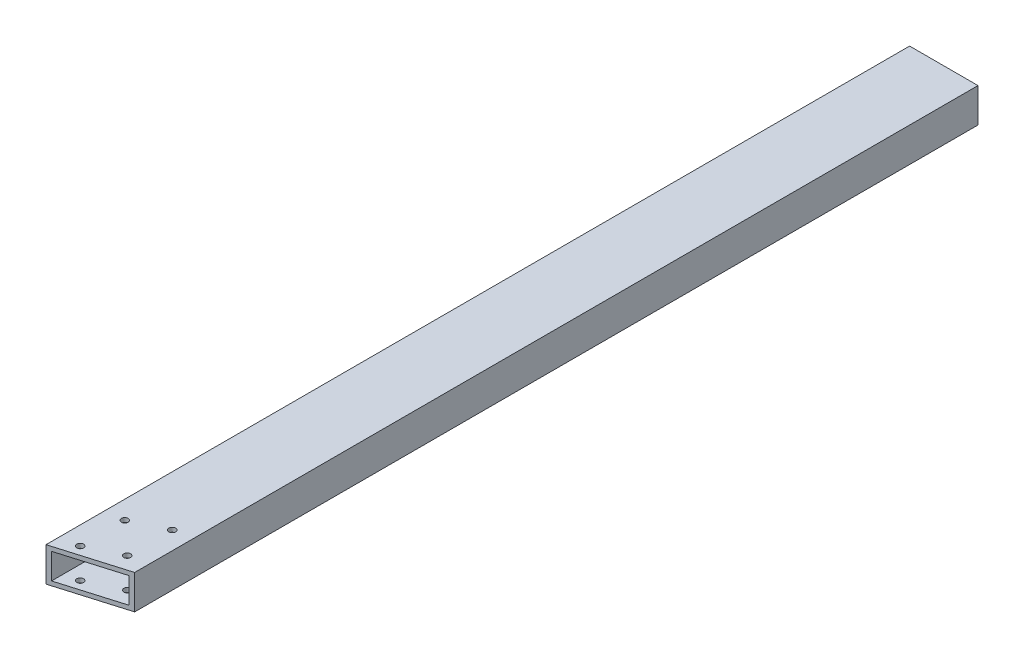
SolidWorks part; units mm, degrees
material "1060 Alloy"
ref_plane "Front Plane" through (0, 0, 0) normal (0, 0, 1) x (1, 0, 0)
ref_plane "Top Plane" through (0, 0, 0) normal (0, 1, 0) x (1, 0, 0)
ref_plane "Right Plane" through (0, 0, 0) normal (1, 0, 0) x (0, 0, -1)
sketch "Sketch1" plane through (0, 0, 0) normal (0, 0, 1) x (1, 0, 0)
  line L0 (-22.225, 9.525) -> (22.225, 9.525)
  line L2 (-25.4, 12.7) -> (25.4, 12.7)
  line L3 (-25.4, 12.7) -> (-25.4, -12.7)
  line L4 (-25.4, -12.7) -> (25.4, -12.7)
  line L5 (25.4, 12.7) -> (25.4, -12.7)
  line L10 (22.225, 9.525) -> (22.225, -9.525)
  line L11 (-22.225, -9.525) -> (22.225, -9.525)
  line L12 (-22.225, 9.525) -> (-22.225, -9.525)
  point P12 (0, 12.7)
  point P14 (25.4, 0)
  dimension "Wall Thickness" = 3.175
  dimension "Outside Width" = 50.8
  dimension "Outside Height" = 25.4
  dimension "Inside Height" = 19.05
  dimension "Inside Width" = 44.45
sketch "Sketch2" plane through (0, 0, 0) normal (1, 0, 0) x (0, 0, -1)
  line L0 (320.675, 0) -> (-320.675, 0)
  point P4 (0, 0)
  point P7 (-320.675, 0)
  point P10 (320.675, 0)
  dimension "Length" = 641.35
sketch "Sketch3" plane through (0, 0, 0) normal (0, 0, 1) x (1, 0, 0)
  line L21 (25.4, 12.7) -> (-25.4, 12.7)
  line L22 (25.4, -12.7) -> (25.4, 12.7)
  line L23 (-25.4, -12.7) -> (25.4, -12.7)
  line L24 (-25.4, 12.7) -> (-25.4, -12.7)
  line L25 (25.4, 12.7) -> (-25.4, 12.7)
  line L26 (25.4, -12.7) -> (25.4, 12.7)
  line L27 (-25.4, -12.7) -> (25.4, -12.7)
  line L28 (-25.4, 12.7) -> (-25.4, -12.7)
  line L29 (22.225, 9.525) -> (-22.225, 9.525)
  line L30 (22.225, -9.525) -> (22.225, 9.525)
  line L31 (-22.225, -9.525) -> (22.225, -9.525)
  line L32 (-22.225, 9.525) -> (-22.225, -9.525)
  line L33 (22.225, 9.525) -> (-22.225, 9.525)
  line L34 (22.225, -9.525) -> (22.225, 9.525)
  line L35 (-22.225, -9.525) -> (22.225, -9.525)
  line L36 (-22.225, 9.525) -> (-22.225, -9.525)
  dimension "D1" = 0
  dimension "D2" = 0
extrude "Boss-Extrude1" add sketch "Sketch3" along normal up to vertex (320.675 mm away) and the other way up to vertex (320.675 mm away) up to point (0, 0, 320.675) other way up to point (0, 0, -320.675)
sketch "Drawing Reference" plane through (0, 0, 0) normal (1, 0, 0) x (0, 0, -1)
  line L0 (-320.675, 0) -> (320.675, 0) construction
  line L1 (0, -12.7) -> (0, 12.7) construction
  line L2 (-320.675, -12.7) -> (320.675, -12.7) construction
  line L5 (-320.675, 12.7) -> (320.675, 12.7) construction
  point P7 (-284.099, 0)
  point P8 (284.099, 0)
  dimension "D1" = 36.576
sketch "Sketch4" plane through (0, 12.7, 0) normal (0, 1, 0) x (1, 0, 0)
  line L0 (-25.4, -320.675) -> (25.4, -305.6274)
  line L1 (25.4, -320.675) -> (25.4, 320.675) construction
  line L2 (25.4, -320.675) -> (-25.4, -320.675)
  dimension "D1" = 16.5
extrude "Cut-Extrude1" cut sketch "Sketch4" against normal through all and the other way through all flip side to cut
sketch "Sketch6" plane through (0, -12.7, 0) normal (0, -1, 0) x (1, 0, 0)
  line L0 (25.4, 305.6274) -> (22.1108, 294.5233) construction
  line L1 (25.4, 279.2824) -> (22.225, 279.2824) construction
  line L2 (25.4, 305.6274) -> (25.4, -320.675) construction
  line L3 (22.225, 279.2824) -> (22.225, 313.1512) construction
  line L4 (22.1108, 294.5233) -> (11.811, 297.5742) construction
  line L5 (-11.811, 250.3501) -> (-11.811, 328.3651) construction
  line L6 (-25.4, 320.675) -> (-27.5213, 313.5136) construction
  line L7 (-25.4, 287.6223) -> (-22.225, 287.6223) construction
  line L8 (-25.4, 320.675) -> (-25.4, -320.675) construction
  line L9 (-22.225, 287.6223) -> (-22.225, 328.3651) construction
  line L10 (-27.5213, 313.5136) -> (-11.811, 308.86) construction
  line L11 (11.811, 250.3501) -> (11.811, 313.1512) construction
  line L12 (-27.5213, 313.5136) -> (-36.5388, 283.071) construction
  line L13 (22.1108, 294.5233) -> (13.0933, 264.0807) construction
  line L14 (-37.6746, 250.3501) -> (48.6057, 250.3501) construction
  line L15 (-11.811, 287.6223) -> (-11.811, 328.3651) construction
  line L16 (11.811, 279.2824) -> (11.811, 313.1512) construction
  line L17 (-36.5388, 283.071) -> (-11.811, 275.7463) construction
  line L18 (13.0933, 264.0807) -> (11.811, 264.4606) construction
  line L19 (-11.811, 308.86) -> (11.811, 264.4606) construction
  line L20 (11.811, 297.5742) -> (-11.811, 275.7463) construction
  point P10 (0, 286.6603)
  dimension "D1" = 10.414
  dimension "D2" = 10.414
hole_wizard "#10 Clearance Hole1" positions "Sketch9" profile "Sketch10" hole size "#10" standard "ANSI Inch"
sketch "Sketch9" plane through (0, 12.7, 0) normal (0, 1, 0) x (1, 0, 0)
  line L0 (13.0933, -264.0807) -> (11.811, -264.4606) construction
  point P0 (-11.811, -275.7463)
  point P3 (-11.811, -308.86)
  point P6 (11.811, -297.5742)
  point P9 (12.0472, -264.3906)
sketch "Sketch10" plane through (-11.811, 12.7, 275.7463) normal (1, 0, 0) x (0, 0, 1)
  line L0 (0, 0) -> (0, 31.9757)
  line L1 (0, 31.9757) -> (2.4892, 30.48)
  line L2 (2.4892, 30.48) -> (2.4892, 0)
  line L5 (2.4892, 0) -> (0, 0)
  line L10 (0, 31.9757) -> (-2.4892, 30.48) construction
  line L11 (0, -6.35) -> (0, 107.95) construction
  dimension "Hole Dia." = 4.9784
  dimension "Hole Depth" = 30.48
  dimension "Drill Angle" = 118
equation "\"D1@Drawing Reference\"=\"Outside Width@Sketch1\" * 0.72"
